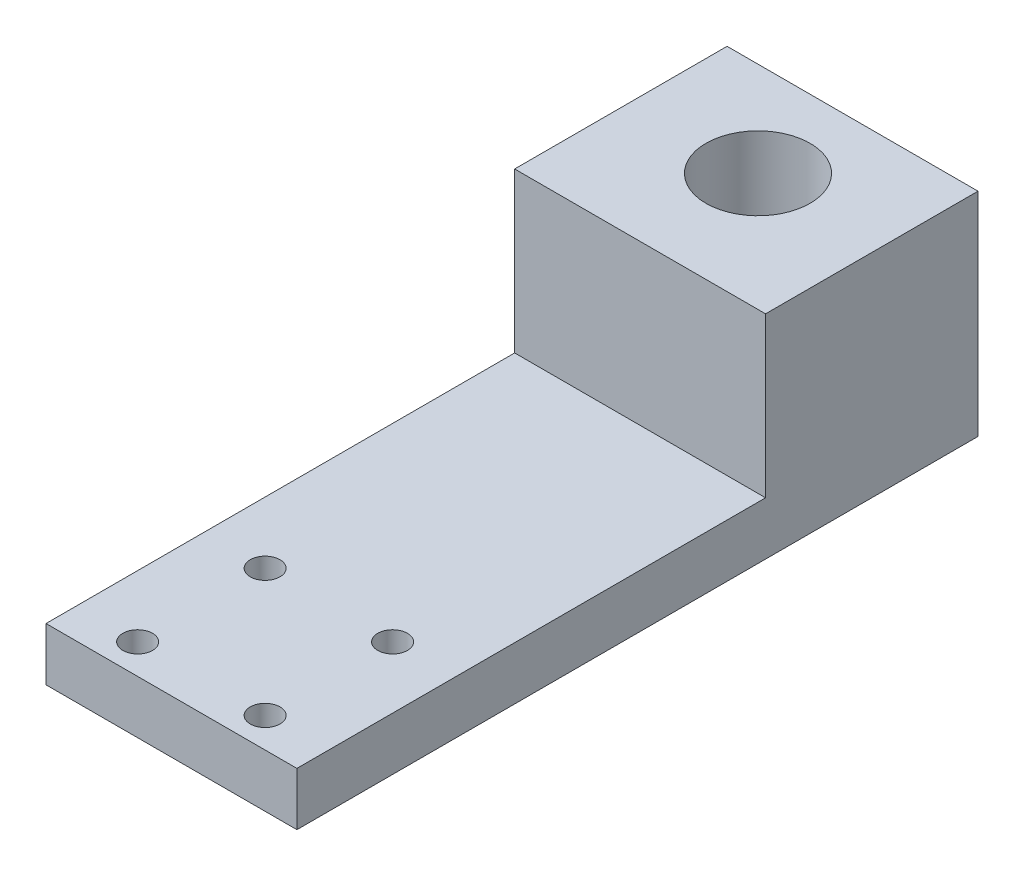
SolidWorks part; units mm, degrees
ref_plane "Front Plane" through (0, 0, 0) normal (0, 0, 1) x (1, 0, 0)
ref_plane "Top Plane" through (0, 0, 0) normal (0, 1, 0) x (1, 0, 0)
ref_plane "Right Plane" through (0, 0, 0) normal (1, 0, 0) x (0, 0, -1)
sketch "Sketch1" plane through (0, 0, 0) normal (0, 1, 0) x (1, 0, 0)
  line L0 (3.69, -31.3062) -> (11.31, -31.3062) construction
  line L1 (0, 0) -> (15, 0)
  line L2 (0, 0) -> (0, -40.7162)
  line L3 (0, -40.7162) -> (15, -40.7162)
  line L4 (15, 0) -> (15, -40.7162)
  line L5 (0, -12.7) -> (15, -12.7)
  circle A0 centre (3.69, -31.3062) radius 0.889
  circle A1 centre (11.31, -31.3062) radius 0.889
  circle A2 centre (11.31, -38.9262) radius 0.889
  circle A3 centre (3.69, -38.9262) radius 0.889
  circle A4 centre (7.5, -5.6515) radius 3.1115
  point P13 (7.5, -31.3062)
  point P14 (7.5, -40.7162)
  point P17 (7.5, 0)
  dimension "D5" = 1.778
  dimension "D7" = 6.223
  dimension "D1" = 15
  dimension "D2" = 40.7162
  dimension "D3" = 7.62
  dimension "D4" = 7.62
  dimension "D6" = 1.79
  dimension "D8" = 5.6515
  dimension "D9" = 12.7
extrude "Boss-Extrude1" add sketch "Sketch1" along normal blind 3.175 contours L5 L2 L3 L4 A3 A2 A0 A1 region at (7.5, 0, 26.5046)
extrude "Boss-Extrude2" add sketch "Sketch1<3>" along normal blind 12.7 contours L2 L5 L4 L1 A4 region at (7.5, 0, 0.1965)
sketch "Sketch1<3>" plane through (0, 0, 0) normal (0, 1, 0) x (1, 0, 0) same geometry as "Sketch1"
equation "\"D4@Sketch1\"=\"D3@Sketch1\""
equation "\"D8@Sketch1\"=\"D7@Sketch1\"/2 +0.1in"
